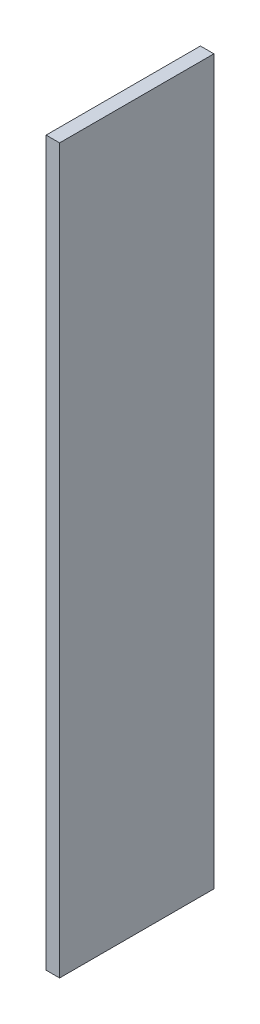
SolidWorks part; units mm, degrees
ref_plane "Front Plane" through (0, 0, 0) normal (0, 0, 1) x (1, 0, 0)
ref_plane "Top Plane" through (0, 0, 0) normal (0, 1, 0) x (1, 0, 0)
ref_plane "Right Plane" through (0, 0, 0) normal (1, 0, 0) x (0, 0, -1)
sketch "Sketch1" plane through (0, 0, 0) normal (1, 0, 0) x (0, 0, -1)
  line L1 (-8, -37.5) -> (8, -37.5)
  line L2 (-8, -37.5) -> (-8, 37.5)
  line L3 (-8, 37.5) -> (8, 37.5)
  line L4 (8, -37.5) -> (8, 37.5)
  line L5 (-8, -37.5) -> (8, 37.5) construction
  line L6 (-8, 37.5) -> (8, -37.5) construction
  point P0 (0, 0)
  dimension "D1" = 75
  dimension "D2" = 16
extrude "Boss-Extrude4" add sketch "Sketch1" along normal blind 1.4
